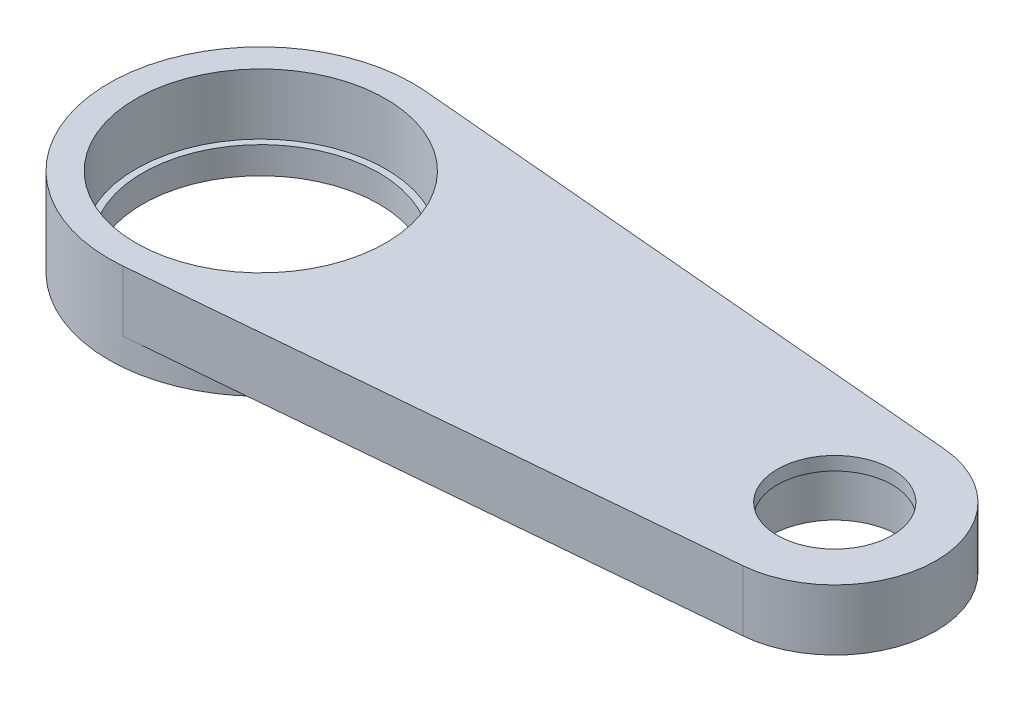
SolidWorks part; units mm, degrees
other "마크업1"
sketch "스케치8" plane through (80, 10, 22.5) normal (0.0741, 0.9433, 0.3234) x (0.9972, -0.0727, -0.0163)
ref_plane "정면" through (0, 0, 0) normal (0, 0, 1) x (1, 0, 0)
ref_plane "윗면" through (0, 0, 0) normal (0, 1, 0) x (1, 0, 0)
ref_plane "우측면" through (0, 0, 0) normal (1, 0, 0) x (0, 0, -1)
sketch "스케치1" plane through (0, 0, 0) normal (0, 1, 0) x (1, 0, 0)
  circle A0 centre (0, 0) radius 17.5
  circle A1 centre (0, 0) radius 22.5
  dimension "D1" = 35
  dimension "D2" = 45
extrude "보스-돌출1" add sketch "스케치1" along normal blind 8 contours A1 | A0
sketch "스케치2" plane through (0, 8, 0) normal (0, 1, 0) x (1, 0, 0)
  circle A0 centre (0, 0) radius 18.5
  circle A1 centre (0, 0) radius 22.5 construction
  circle A2 centre (0, 0) radius 22.5
  dimension "D1" = 37
extrude "보스-돌출2" add sketch "스케치2" along normal blind 5
sketch "스케치3" plane through (0, 13, 0) normal (0, 1, 0) x (1, 0, 0)
  line L0 (1.9853, 22.4122) -> (86.3235, 14.9415)
  line L1 (0, 0) -> (85, 0) construction
  line L2 (1.9853, -22.4122) -> (86.3235, -14.9415)
  circle A0 centre (0, 0) radius 22.5 construction
  arc A1 (1.9853, -22.4122) -> (1.9853, 22.4122) centre (0, 0) ccw
  arc A2 (86.3235, -14.9415) -> (86.3235, 14.9415) centre (85, 0) ccw
  dimension "D2" = 30
  dimension "D1" = 85
extrude "보스-돌출3" add sketch "스케치3" against normal blind 9
sketch "스케치7" plane through (0, 8, 0) normal (0, 1, 0) x (1, 0, 0)
  circle A0 centre (0, 0) radius 18.5 construction
  circle A1 centre (0, 0) radius 18.5
extrude "컷-돌출4" cut sketch "스케치7" against normal blind 4
sketch "스케치13" plane through (0, 4, 0) normal (0, -1, 0) x (1, 0, 0)
  circle A0 centre (85, 0) radius 9.5
  dimension "D1" = 19
extrude "컷-돌출9" cut sketch "스케치13" against normal blind 7
sketch "스케치14" plane through (0, 11, 0) normal (0, -1, 0) x (1, 0, 0)
  circle A0 centre (85, 0) radius 8.5
  dimension "D1" = 17
extrude "컷-돌출10" cut sketch "스케치14" against normal through all
